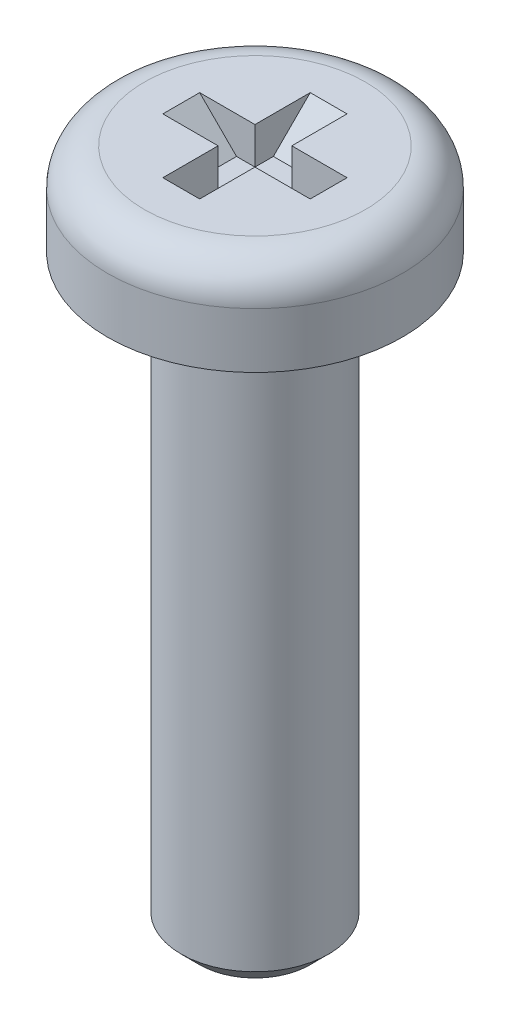
SolidWorks part; units mm, degrees
ref_plane "前视基准面" through (0, 0, 0) normal (0, 0, 1) x (1, 0, 0)
ref_plane "上视基准面" through (0, 0, 0) normal (0, 1, 0) x (1, 0, 0)
ref_plane "右视基准面" through (0, 0, 0) normal (1, 0, 0) x (0, 0, -1)
other "Configuration Table"
sketch "草图1" plane through (0, 0, 0) normal (0, 1, 0) x (1, 0, 0)
  circle A0 centre (0, 0) radius 2
  dimension "D1" = 4
extrude "凸台-拉伸1" add sketch "草图1" along normal blind 16
cosmetic thread "装饰螺纹线1" parameters "D2"=3
sketch "草图2" plane through (0, 16, 0) normal (0, 1, 0) x (1, 0, 0)
  circle A0 centre (0, 0) radius 4
  dimension "D1" = 8
extrude "凸台-拉伸2" add sketch "草图2" along normal blind 2.5
fillet "圆角1" radius 1 1 edges at (0, 18.5, 4)
chamfer "倒角1" distance 0.5 angle 45 1 edges at (0, 0, 2)
sketch "草图3" plane through (0, 18.5, 0) normal (0, 1, 0) x (1, 0, 0)
  line L0 (-2, 0) -> (2, 0)
  line L1 (0, 2) -> (0, -2)
  point P5 (0, 0)
  point P9 (0, 0)
  dimension "D1" = 4
  dimension "D2" = 4
extrude "切除-拉伸-薄壁1" cut sketch "草图3" against normal blind 1 thin thin type mid plane wall 1
chamfer "倒角2" distance 1 angle 45 4 edges at (0, 17.5, 2) (2, 17.5, 0) (0, 17.5, -2) (-2, 17.5, 0)
